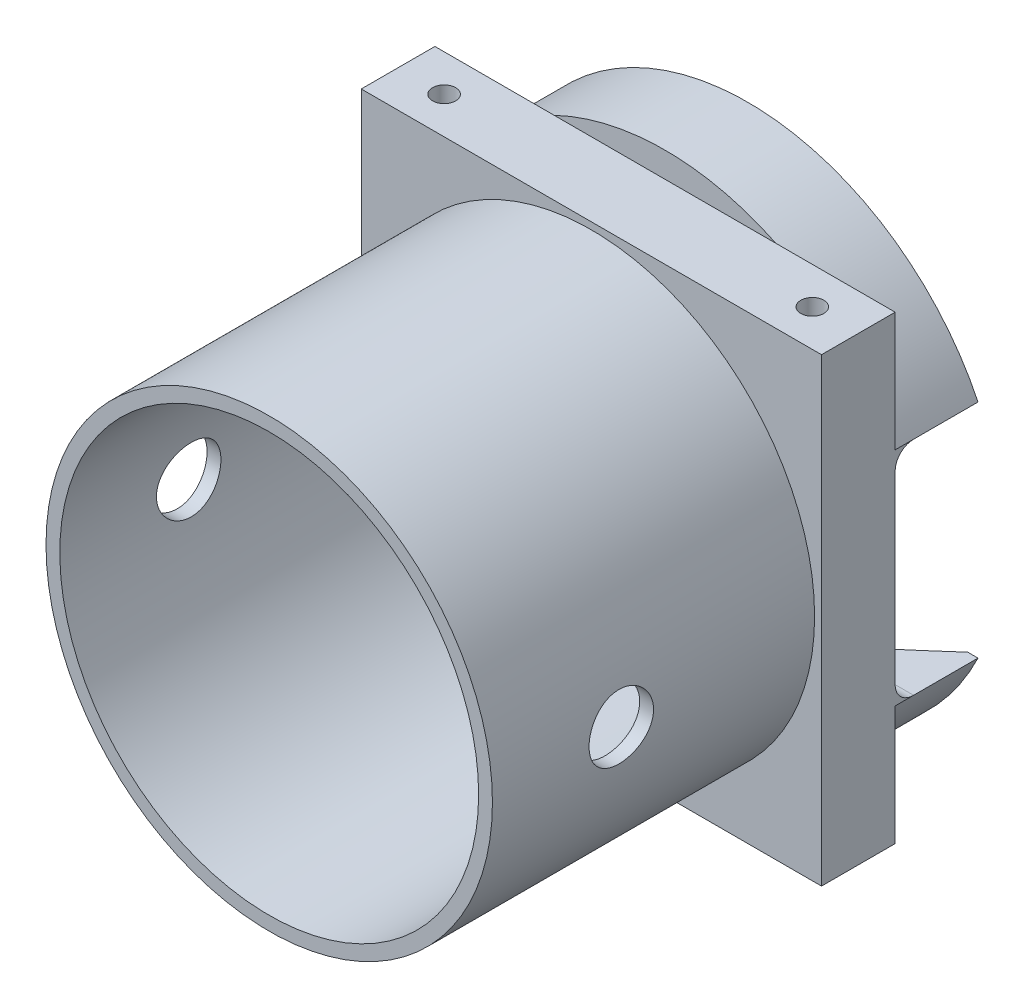
SolidWorks part; units mm, degrees
material "6061 合金"
ref_plane "前视基准面" through (0, 0, 0) normal (0, 0, 1) x (1, 0, 0)
ref_plane "上视基准面" through (0, 0, 0) normal (0, 1, 0) x (1, 0, 0)
ref_plane "右视基准面" through (0, 0, 0) normal (1, 0, 0) x (0, 0, -1)
sketch "草图1" plane through (0, 0, 0) normal (0, 0, 1) x (1, 0, 0)
  circle A0 centre (0, 0) radius 24.25
  circle A1 centre (0, 0) radius 22.75
  dimension "D1" = 48.5
  dimension "D2" = 45.5
  dimension "D3" = 1.5
extrude "凸台-拉伸1" add sketch "草图1" along normal blind 35
sketch "草图2" plane through (0, 0, 0) normal (0, 0, -1) x (-1, 0, 0)
  line L1 (-25, -25) -> (25, -25)
  line L2 (-25, -25) -> (-25, 25)
  line L3 (-25, 25) -> (25, 25)
  line L4 (25, -25) -> (25, 25)
  line L5 (0, 25) -> (0, -25) construction
  line L6 (-25, 0) -> (25, 0) construction
  circle A0 centre (0, 0) radius 22.75 construction
  circle A1 centre (0, 0) radius 22.75
  point P0 (0, 0)
  dimension "D1" = 50
extrude "凸台-拉伸2" add sketch "草图2" along normal blind 8
hole_wizard "M3 螺纹孔1" positions "草图3" profile "草图4" tap size "M3" standard "GB"
sketch "草图3" plane through (0, 25, 0) normal (0, 1, 0) x (1, 0, 0)
  line L0 (-20, 4) -> (20, 4) construction
  line L3 (0, 0) -> (0, 4) construction
  line L6 (-25, 8) -> (-25, 0) construction
  point P1 (-20, 4)
  point P2 (20, 4)
  point P13 (-25, 4)
  dimension "D1" = 40
cosmetic thread "孔螺蚊线1" parameters "D1"=6, "D2"=3
cosmetic thread "孔螺蚊线2" parameters "D1"=6, "D2"=3
sketch "草图4" plane through (-20, 25, -4) normal (1, 0, 0) x (0, 0, 1)
  line L0 (0, 0) -> (0, 7.7511)
  line L1 (0, 7.7511) -> (1.25, 7)
  line L2 (1.25, 7) -> (1.25, 0)
  line L5 (1.25, 0) -> (0, 0)
  line L10 (0, 7.7511) -> (-1.25, 7) construction
  line L11 (0, -6.35) -> (0, 107.95) construction
  dimension "螺纹孔钻头直径" = 2.5
  dimension "螺纹孔钻头深度" = 7
  dimension "导头角度" = 118
sketch "草图5" plane through (0, 0, -8) normal (0, 0, -1) x (-1, 0, 0)
  line L0 (-25, -12.0442) -> (-19.3003, -12.0442)
  line L1 (-25, 25) -> (-25, -25) construction
  line L2 (0, 23.65) -> (0, -23.65) construction
  line L3 (25, -12.0442) -> (19.3003, -12.0442)
  line L4 (23.65, 0) -> (-23.65, 0) construction
  line L5 (25, 12.0442) -> (19.3003, 12.0442)
  line L6 (-25, 12.0442) -> (-19.3003, 12.0442)
  circle A0 centre (0, 0) radius 22.75 construction
  arc A1 (-19.3003, -12.0442) -> (19.3003, -12.0442) centre (0, 0) ccw
  arc A2 (-25, -12.0442) -> (25, -12.0442) centre (0, 0) ccw
  arc A3 (-25, 12.0442) -> (25, 12.0442) centre (0, 0) cw
  arc A4 (-19.3003, 12.0442) -> (19.3003, 12.0442) centre (0, 0) cw
  dimension "D1" = 5
extrude "凸台-拉伸3" add sketch "草图5" along normal blind 9
sketch "草图6" plane through (0, 0, 0) normal (1, 0, 0) x (0, 0, -1)
  circle A0 centre (-21, 0) radius 3.5
  dimension "D2" = 7
  dimension "D1" = 21
extrude "切除-拉伸1" cut sketch "草图6" against normal through all both and the other way through all
chamfer "倒角2" distance 4 angle 45 2 edges at (0, -22.75, -17) (0, 22.75, -17)
fillet "圆角1" radius 2 4 edges at (-22.1501, -12.0442, -8) (-22.1501, 12.0442, -8) (22.1501, 12.0442, -8) (22.1501, -12.0442, -8)
mirror "镜向1" about plane through (0, 0, 0) normal (0, 1, 0) of "M3 螺纹孔1"
